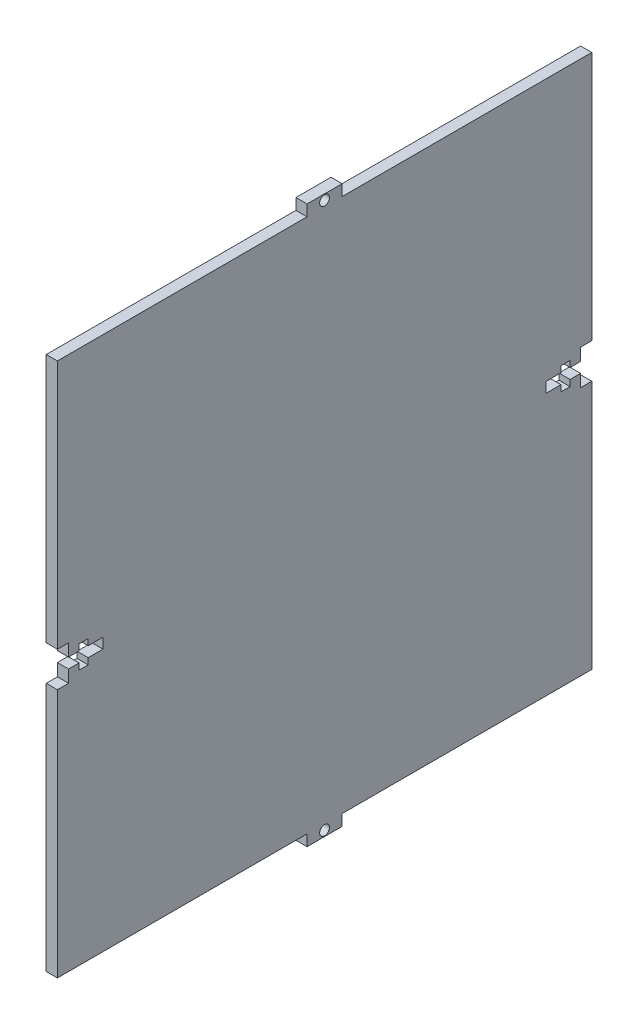
SolidWorks part; units mm, degrees
ref_plane "Front Plane" through (0, 0, 0) normal (0, 0, 1) x (1, 0, 0)
ref_plane "Top Plane" through (0, 0, 0) normal (0, 1, 0) x (1, 0, 0)
ref_plane "Right Plane" through (0, 0, 0) normal (1, 0, 0) x (0, 0, -1)
sketch "Sketch1" plane through (0, 0, 0) normal (1, 0, 0) x (0, 0, -1)
  line L1 (76.2, 76.2) -> (-76.2, 76.2)
  line L2 (76.2, 76.2) -> (76.2, -76.2)
  line L3 (76.2, -76.2) -> (-76.2, -76.2)
  line L4 (-76.2, 76.2) -> (-76.2, -76.2)
  line L5 (76.2, 76.2) -> (-76.2, -76.2) construction
  line L6 (76.2, -76.2) -> (-76.2, 76.2) construction
  point P0 (0, 0)
  dimension "D1" = 152.4
  dimension "D2" = 152.4
extrude "Boss-Extrude1" add sketch "Sketch1" along normal blind 3.18
sketch "Sketch3" plane through (0, 0, 0) normal (-1, 0, 0) x (0, 0, 1)
  line L1 (0, 0) -> (-76.2, 0) construction
  line L2 (-76.2, -76.2) -> (-76.2, 76.2) construction
  line L3 (0, -76.2) -> (0, 76.2) construction
  line L9 (0, 0) -> (76.2, 0) construction
  line L10 (76.2, -76.2) -> (-76.2, -76.2) construction
  line L12 (76.2, 76.2) -> (76.2, -76.2) construction
  line L13 (-76.2, 76.2) -> (76.2, 76.2) construction
  line L14 (5, -76.2) -> (-5, -76.2)
  line L15 (5, -79.38) -> (-5, -79.38)
  line L16 (5, -79.38) -> (5, -76.2)
  line L18 (-5, -79.38) -> (-5, -76.2)
  line L22 (0, -79.38) -> (0, -70.042) construction
  line L23 (5, -77.79) -> (-5, -77.79) construction
  line L27 (5, 76.2) -> (5, 79.38)
  line L28 (5, 79.38) -> (-5, 79.38)
  line L29 (-5, 76.2) -> (-5, 79.38)
  line L30 (5, 77.79) -> (-5, 77.79) construction
  line L31 (0, 76.2) -> (0, 79.38) construction
  line L32 (5, 76.2) -> (-5, 76.2)
  line L33 (0, 57.9987) -> (0, 76.2)
  circle A0 centre (0, -77.79) radius 1.4
  circle A1 centre (0, 77.79) radius 1.4
  point P31 (0, 67.0994)
  line M14 (76.2, 76.2) -> (-76.2, 76.2)
  line M16 (-76.2, -76.2) -> (76.2, -76.2)
  dimension "D5" = 2.8
  dimension "D6" = 2.8
  dimension "D2" = 10
  dimension "D3" = 3.18
  dimension "D4" = 10
  dimension "D1" = 3.18
extrude "Boss-Extrude5" add sketch "Sketch3" against normal blind 3.18 contours L29 L32 L27 L28 A1 M14 | L18 L15 L16 A0 M16 region at (0, -77.79, 4.8951) region at (0, 76.3049, 2.5)
sketch "Sketch4" plane through (0, 0, 0) normal (1, 0, 0) x (0, 0, -1)
  line L2 (0, 0) -> (-76.2, 0) construction
  line L3 (-76.2, 76.2) -> (-76.2, -76.2) construction
  line L4 (-76.2, -5) -> (-76.2, 5)
  line L5 (-76.2, -5) -> (-73.02, -5)
  line L7 (-76.2, 5) -> (-73.02, 5)
  line L8 (-73.02, -5) -> (-73.02, -1.47)
  line L9 (-73.02, 1.47) -> (-73.02, 5)
  line L10 (-73.02, -1.47) -> (-70.02, -1.47)
  line L12 (-73.02, 1.47) -> (-70.02, 1.47)
  line L13 (-63.2, -1.47) -> (-63.2, 1.47)
  line L14 (-67.42, -1.47) -> (-63.2, -1.47)
  line L15 (-70.02, -3.25) -> (-67.42, -3.25)
  line L16 (-70.02, -3.25) -> (-70.02, -1.47)
  line L17 (-70.02, 3.25) -> (-67.42, 3.25)
  line L18 (-67.42, -3.25) -> (-67.42, -1.47)
  line L19 (-67.42, 1.47) -> (-63.2, 1.47)
  line L20 (-70.02, 1.47) -> (-70.02, 3.25)
  line L21 (-67.42, 1.47) -> (-67.42, 3.25)
  dimension "D1" = 3.18
  dimension "D2" = 10
  dimension "D3" = 2.94
  dimension "D4" = 6.5
  dimension "D5" = 2.6
  dimension "D6" = 13
  dimension "D7" = 3
extrude "Cut-Extrude2" cut sketch "Sketch4" along normal through all contours L18 L14 L13 L19 L21 L17 L20 L12 L9 L7 L4 L5 L8 L10 L16 L15
sketch "Sketch5" plane through (0, 0, 0) normal (-1, 0, 0) x (0, 0, 1)
  line L0 (0, 0) -> (-76.2, 0) construction
  line L1 (-76.2, -76.2) -> (-76.2, 76.2) construction
  line L2 (-70.02, -1.47) -> (-73.02, -1.47)
  line L3 (-76.2, -5) -> (-73.02, -5)
  line L4 (-76.2, -5) -> (-76.2, 5)
  line L5 (-76.2, 5) -> (-73.02, 5)
  line L6 (-73.02, -5) -> (-73.02, -1.47)
  line L7 (-63.2, -1.47) -> (-67.42, -1.47)
  line L8 (-63.2, -1.47) -> (-63.2, 1.47)
  line L9 (-63.2, 1.47) -> (-67.42, 1.47)
  line L13 (-67.42, 3.25) -> (-70.02, 3.25)
  line L14 (-67.42, 3.25) -> (-67.42, 1.47)
  line L15 (-67.42, -3.25) -> (-70.02, -3.25)
  line L16 (-70.02, 3.25) -> (-70.02, 1.47)
  line L17 (-70.02, -1.47) -> (-70.02, -3.25)
  line L20 (-67.42, -1.47) -> (-67.42, -3.25)
  line L22 (-70.02, 1.47) -> (-73.02, 1.47)
  line L23 (-73.02, 1.47) -> (-73.02, 5)
  point P9 (-39.8999, 0)
  point P13 (0, 0)
  dimension "D1" = 10
  dimension "D2" = 3.18
  dimension "D3" = 3
  dimension "D4" = 2.6
  dimension "D5" = 2.6
  dimension "D6" = 2.94
  dimension "D7" = 13
  dimension "D8" = 6.5
  dimension "D9" = 6.5
  dimension "D10" = 4.22
extrude "Cut-Extrude3" cut sketch "Sketch5" against normal through all
equation "\"sheet\"= 3.18mm"
equation "\"tabW\"= 15mm"
equation "\"4-40Diam\" = 2.94mm"
equation "\"nutDiam\" = 6.5mm"
equation "\"nutThickness\"= 2.6mm"
